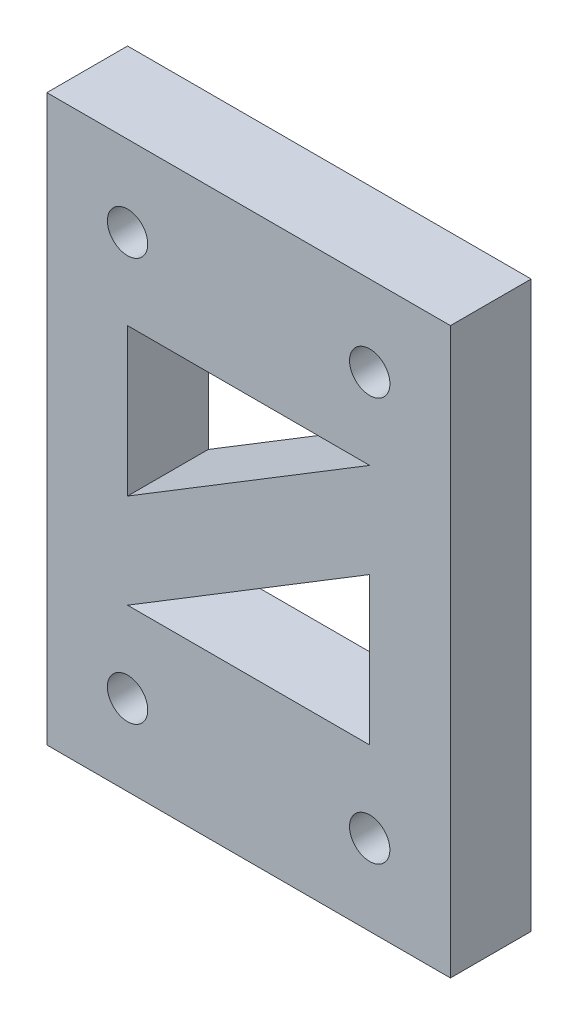
SolidWorks part; units mm, degrees
material "Acrylic (Medium-high impact)"
ref_plane "Front Plane" through (0, 0, 0) normal (0, 0, 1) x (1, 0, 0)
ref_plane "Top Plane" through (0, 0, 0) normal (0, 1, 0) x (1, 0, 0)
ref_plane "Right Plane" through (0, 0, 0) normal (1, 0, 0) x (0, 0, -1)
sketch "Sketch1" plane through (0, 0, 0) normal (0, 0, 1) x (1, 0, 0)
  line L1 (0, 0) -> (50, 0)
  line L2 (0, 0) -> (0, 70)
  line L3 (0, 70) -> (50, 70)
  line L4 (50, 0) -> (50, 70)
  dimension "D1" = 70
  dimension "D2" = 50
base flange "Base-Flange1" sketch "Sketch1" thickness 10 reverse thickness direction no parameters "D1"=0.7366
sketch "Sketch6" plane through (0, 0, 0) normal (0, 0, 1) x (1, 0, 0)
  line L0 (50, 0) -> (50, 70) construction
  line L1 (50, 70) -> (0, 70) construction
  line L2 (0, 35) -> (50, 35) construction
  line L4 (40, 38.2884) -> (40, 20)
  line L5 (40, 20) -> (10, 20)
  line L6 (10, 20) -> (40, 38.2884)
  line L7 (40, 50) -> (10, 31.7116)
  line L8 (10, 31.7116) -> (10, 50)
  line L9 (10, 50) -> (40, 50)
  line L10 (0, 70) -> (0, 0) construction
  circle A0 centre (40, 60) radius 2.5
  circle A1 centre (10, 10) radius 2.5
  circle A2 centre (10, 60) radius 2.5
  circle A3 centre (40, 10) radius 2.5
  dimension "D1" = 5
  dimension "D2" = 10
  dimension "D3" = 10
  dimension "D4" = 50
  dimension "D5" = 30
  dimension "D6" = 10
  dimension "D7" = 10
  dimension "D8" = 10
  dimension "D10" = 10
extrude "Cut-Extrude1" cut sketch "Sketch6" against normal up to next normal cut yes
sketch "Bend-Lines1" [suppressed] plane through (0, 0, 0) normal (0, 1, 0) x (1, 0, 0)
sketch "Bounding-Box1" [suppressed] plane through (0, 0, 0) normal (0, 1, 0) x (1, 0, 0)
sheet metal parameters "Sheet-Metal1" thickness 10 parameters "D1"=0.7366
flat pattern "Flat-Pattern1" [suppressed]
sketch "Bend-Lines2" plane through (0, 0, 0) normal (0, 1, 0) x (1, 0, 0)
sketch "Bounding-Box2" [suppressed] plane through (0, 0, 0) normal (0, 1, 0) x (1, 0, 0)
sheet metal parameters "Sheet-Metal2" thickness 10 parameters "D1"=0.7366
flat pattern "Flat-Pattern1"
sketch "Bend-Lines2" plane through (0, 0, 0) normal (0, 1, 0) x (1, 0, 0)
sketch3d "Bounding-Box2" [suppressed]
  line L0 (50, 80, 0) -> (50, 0, 0) construction
  line L1 (0, 80, 0) -> (0, 0, 0) construction
  line L2 (50, 80, 0) -> (0, 80, 0) construction
  line L3 (50, 0, 0) -> (0, 0, 0) construction
